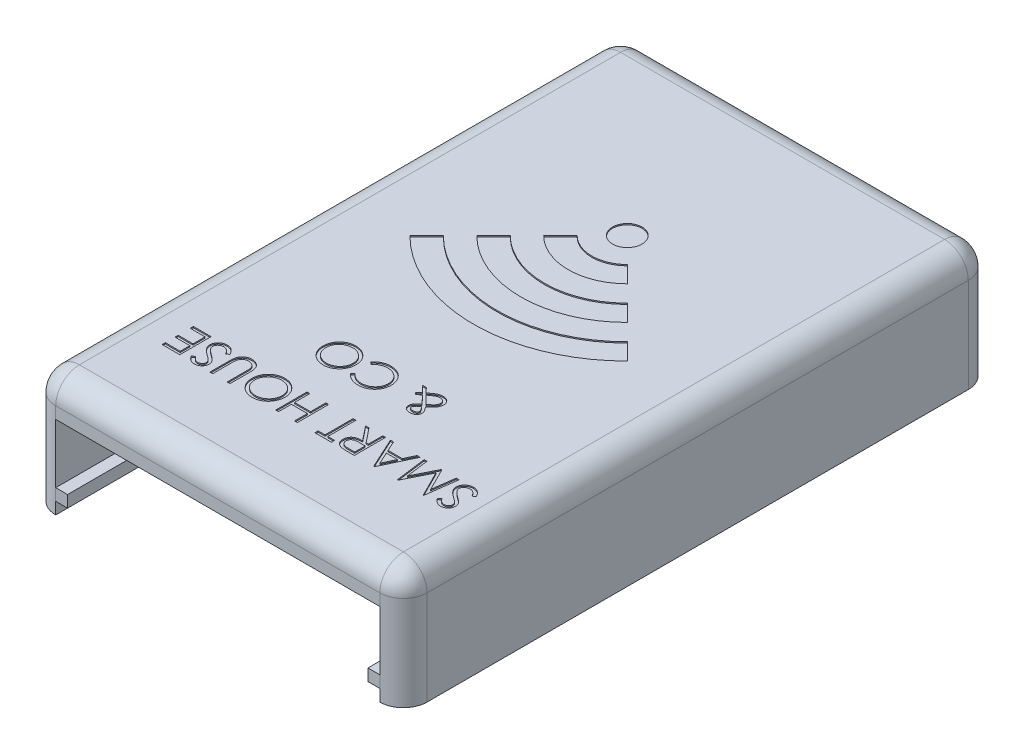
SolidWorks part; units mm, degrees
material "ABS"
ref_plane "Alzado" through (0, 0, 0) normal (0, 0, 1) x (1, 0, 0)
ref_plane "Planta" through (0, 0, 0) normal (0, 1, 0) x (1, 0, 0)
ref_plane "Vista lateral" through (0, 0, 0) normal (1, 0, 0) x (0, 0, -1)
sketch "Croquis1" plane through (0, 0, 0) normal (0, 1, 0) x (1, 0, 0)
  line L1 (15.7, 25.63) -> (-15.7, 25.63)
  line L2 (15.7, 25.63) -> (15.7, -25.63)
  line L3 (15.7, -25.63) -> (-15.7, -25.63)
  line L4 (-15.7, 25.63) -> (-15.7, -25.63)
  line L5 (15.7, 25.63) -> (-15.7, -25.63) construction
  line L6 (15.7, -25.63) -> (-15.7, 25.63) construction
  point P0 (0, 0)
  dimension "D1" = 31.4
  dimension "D2" = 51.26
extrude "Saliente-Extruir1" add sketch "Croquis1" along normal blind 15
sketch "Croquis18" plane through (0, 0, 0) normal (0, -1, 0) x (1, 0, 0)
  line L0 (-15.7, -25.63) -> (-15.7, 25.63) construction
  line L1 (-13.7, 25.13) -> (13.7, 25.13)
  line L2 (-13.7, 25.13) -> (-13.7, -23.63)
  line L3 (-13.7, -23.63) -> (13.7, -23.63)
  line L4 (13.7, 25.13) -> (13.7, -23.63)
  line L5 (15.7, -25.63) -> (-15.7, -25.63) construction
  line L6 (-15.7, 25.63) -> (15.7, 25.63) construction
  line L7 (15.7, 25.63) -> (15.7, -25.63) construction
  dimension "D1" = 2
  dimension "D2" = 2
  dimension "D3" = 0.5
  dimension "D4" = 2
extrude "Cortar-Extruir16" cut sketch "Croquis18" against normal blind 13
sketch "Croquis19" plane through (0, 0, -23.63) normal (0, 0, 1) x (1, 0, 0)
  line L1 (-13.7, 0) -> (13.7, 0)
  line L2 (-13.7, 0) -> (-13.7, 13)
  line L3 (-13.7, 13) -> (13.7, 13)
  line L4 (13.7, 0) -> (13.7, 13)
extrude "Cortar-Extruir17" cut sketch "Croquis19" against normal blind 1
sketch "Croquis20" plane through (0, 0, 0) normal (0, -1, 0) x (-1, 0, 0)
  line L0 (13.7, 24.63) -> (-13.7, 24.63) construction
  line L1 (13.7, 24.63) -> (-13.7, 24.63)
  line L2 (13.7, 24.63) -> (13.7, -24.63)
  line L3 (13.7, -24.63) -> (-13.7, -24.63)
  line L4 (-13.7, 24.63) -> (-13.7, -24.63)
  line L5 (13.7, -25.13) -> (13.7, 24.63) construction
  line L6 (-13.7, 24.63) -> (-13.7, -25.13) construction
  line L8 (13.7, -24.63) -> (-13.7, -24.63)
  line L9 (13.7, -24.63) -> (13.7, -25.13)
  line L10 (13.7, -25.13) -> (-13.7, -25.13)
  line L11 (-13.7, -24.63) -> (-13.7, -25.13)
  line M2 (13.7, 24.63) -> (13.7, -25.13)
  line M3 (13.7, -25.13) -> (-13.7, -25.13)
  line M4 (-13.7, -25.13) -> (-13.7, 24.63)
  dimension "D1" = 0
  dimension "D2" = 0
  dimension "D3" = 0
  dimension "D4" = 49.26
extrude "Saliente-Extruir2" add sketch "Croquis20" against normal blind 13 contours L3 M2 M4 M3 region at (0, 0, 24.88)
sketch "Croquis22" plane through (0, 0, -25.63) normal (0, 0, -1) x (-1, 0, 0)
  line L1 (-20.4787, 17.3938) -> (19.0653, 17.3938)
  line L2 (-20.4787, 17.3938) -> (-20.4787, -3.022)
  line L3 (-20.4787, -3.022) -> (19.0653, -3.022)
  line L4 (19.0653, 17.3938) -> (19.0653, -3.022)
extrude "Cortar-Extruir18" cut sketch "Croquis22" against normal blind 0.5
sketch "Croquis23" plane through (0, 0, 25.63) normal (0, 0, 1) x (1, 0, 0)
  line L0 (13.7, 13) -> (13.7, 0) construction
  line L1 (-13.7, 0) -> (13.7, 0)
  line L2 (-13.7, 0) -> (-13.7, 5)
  line L3 (-13.7, 5) -> (13.7, 5)
  line L4 (13.7, 0) -> (13.7, 5)
  dimension "D1" = 5
extrude "Cortar-Extruir20" cut sketch "Croquis23" against normal blind 5
sketch "Croquis24" plane through (0, 0, 25.63) normal (0, 0, 1) x (1, 0, 0)
  line L0 (-13.7, 2) -> (-12.7, 2)
  line L1 (-13.7, 2) -> (-13.7, 1)
  line L2 (-12.7, 1) -> (-13.7, 1)
  line L3 (-12.7, 1) -> (-12.7, 2)
  line L4 (0, 5) -> (0, 0)
  line L5 (-15.7, 0) -> (-13.7, 0) construction
  line L6 (13.7, 5) -> (-13.7, 5) construction
  line L7 (0, 2.5) -> (-2.2352, 2.5)
  line L9 (12.7, 1) -> (12.7, 2)
  line L10 (12.7, 1) -> (13.7, 1)
  line L11 (13.7, 2) -> (13.7, 1)
  line L12 (13.7, 2) -> (12.7, 2)
  line M2 (-13.7, 0) -> (-13.7, 5)
  line M4 (13.7, 5) -> (13.7, 0)
  dimension "D1" = 1
extrude "Saliente-Extruir4" add sketch "Croquis24" against normal blind 50.46 contours L2 L3 L0 M2 | L12 L9 L10 M4 region at (-13.2, 1.5, 25.63) region at (13.2, 1.5, 25.63)
sketch "Croquis25" plane through (0, 5, 0) normal (0, -1, 0) x (1, 0, 0)
  line L1 (-13.7, 25.63) -> (13.7, 25.63)
  line L2 (-13.7, 25.63) -> (-13.7, 24.63)
  line L3 (-13.7, 24.63) -> (13.7, 24.63)
  line L4 (13.7, 25.63) -> (13.7, 24.63)
extrude "Cortar-Extruir21" cut sketch "Croquis25" against normal blind 2
sketch "Croquis26" plane through (0, 15, 0) normal (0, 1, 0) x (1, 0, 0)
  line L1 (-15.7, 25.13) -> (15.7, 25.13)
  line L2 (-15.7, 25.13) -> (-15.7, -25.63)
  line L3 (-15.7, -25.63) -> (15.7, -25.63)
  line L4 (15.7, 25.13) -> (15.7, -25.63)
extrude "Cortar-Extruir23" cut sketch "Croquis26" against normal blind 5
sketch "Croquis27" plane through (-13.7, 0, 0) normal (1, 0, 0) x (0, 0, -1)
  line L0 (24.63, 10) -> (24.63, 2) construction
  line L1 (-24.63, 10) -> (24.63, 10)
  line L2 (-24.63, 10) -> (-24.63, 8)
  line L3 (-24.63, 8) -> (24.63, 8)
  line L4 (24.63, 10) -> (24.63, 8)
  dimension "D1" = 2
extrude "Saliente-Extruir5" add sketch "Croquis27" along normal blind 28
sketch "Croquis28" plane through (0, 0, -25.13) normal (0, 0, -1) x (-1, 0, 0)
  line L0 (0, 0) -> (0, 3)
  line L1 (-3, 3) -> (3, 3)
  line L2 (3, 3) -> (4, 4.218)
  line L3 (-3, 3) -> (-4, 4.218)
  line L4 (-4, 4.218) -> (-4, 6.218)
  line L5 (4, 6.218) -> (-4, 6.218)
  line L6 (4, 4.218) -> (4, 6.218)
  line L7 (3, 3) -> (4, 4.218)
  circle A0 centre (-3.5, 5.718) radius 0.5
  circle A1 centre (3.5, 5.718) radius 0.5
  point P10 (0, 6.218)
  dimension "D3" = 8
  dimension "D1" = 6
  dimension "D2" = 2
extrude "Cortar-Extruir26" cut sketch "Croquis28" against normal blind 28 contours A1 L5 A0 L4 L3 L1 L2 L6 | A0 | A1 region at (0, 4.5898, -25.13) region at (3.5, 5.718, -25.13) region at (-3.5, 5.718, -25.13)
sketch "Croquis30" plane through (0, 0, 0) normal (0, -1, 0) x (1, 0, 0)
  line L0 (15.7, 25.63) -> (15.7, -25.13) construction
  line L1 (-15.7, 25.63) -> (15.7, 25.63)
  line L2 (-15.7, 25.63) -> (-15.7, 24.63)
  line L3 (-15.7, 24.63) -> (15.7, 24.63)
  line L4 (15.7, 25.63) -> (15.7, 24.63)
  dimension "D1" = 1
extrude "Cortar-Extruir27" cut sketch "Croquis30" against normal blind 28
sketch "Croquis31" plane through (0, 0, 24.63) normal (0, 0, 1) x (1, 0, 0)
  line L0 (13.7, 2) -> (13.7, 8) construction
  line L1 (-13.7, 8) -> (13.7, 8)
  line L2 (-13.7, 8) -> (-13.7, 7)
  line L3 (-13.7, 7) -> (13.7, 7)
  line L4 (13.7, 8) -> (13.7, 7)
  dimension "D1" = 1
extrude "Saliente-Extruir6" add sketch "Croquis31" against normal blind 49
fillet "Redondeo2" radius 2 4 edges at (0, 10, -25.13) (-15.7, 10, -0.25) (15.7, 10, -0.25) (0, 10, 24.63)
fillet "Redondeo3" radius 2 2 edges at (15.1142, 9.4142, -24.5442) (15.7, 4, -25.13)
fillet "Redondeo4" radius 2 6 edges at (-15.1142, 9.4142, -24.5442) (-15.1142, 9.4142, 24.0442) (15.1142, 9.4142, 24.0442) (-15.7, 4, -25.13) (-15.7, 4, 24.63) (15.7, 4, 24.63)
sketch "Croquis32" plane through (0, 10, 0) normal (0, 1, 0) x (1, 0, 0)
  line L1 (-2.1213, 7.8787) -> (-3.5355, 6.4645)
  line L3 (2.1213, 7.8787) -> (3.5355, 6.4645)
  line L4 (7.7782, 2.2218) -> (9.1924, 0.8076)
  line L5 (4.9497, 5.0503) -> (6.364, 3.636)
  line L6 (-7.7782, 2.2218) -> (-9.1924, 0.8076)
  line L7 (-4.9497, 5.0503) -> (-6.364, 3.636)
  arc A0 (-2.1213, 7.8787) -> (2.1213, 7.8787) centre (0, 10) ccw
  arc A1 (-3.5355, 6.4645) -> (3.5355, 6.4645) centre (0, 10) ccw
  arc A2 (-4.9497, 5.0503) -> (4.9497, 5.0503) centre (0, 10) ccw
  arc A3 (-6.364, 3.636) -> (6.364, 3.636) centre (0, 10) ccw
  arc A4 (-9.1924, 0.8076) -> (9.1924, 0.8076) centre (0, 10) ccw
  arc A5 (-7.7782, 2.2218) -> (7.7782, 2.2218) centre (0, 10) ccw
  circle A6 centre (0, 10) radius 1.25
  text T0 "SMART HOUSE \r\n& CO" font "Century Gothic" height in points 10
extrude "Cortar-Extruir28" cut sketch "Croquis32" against normal blind 0.1
